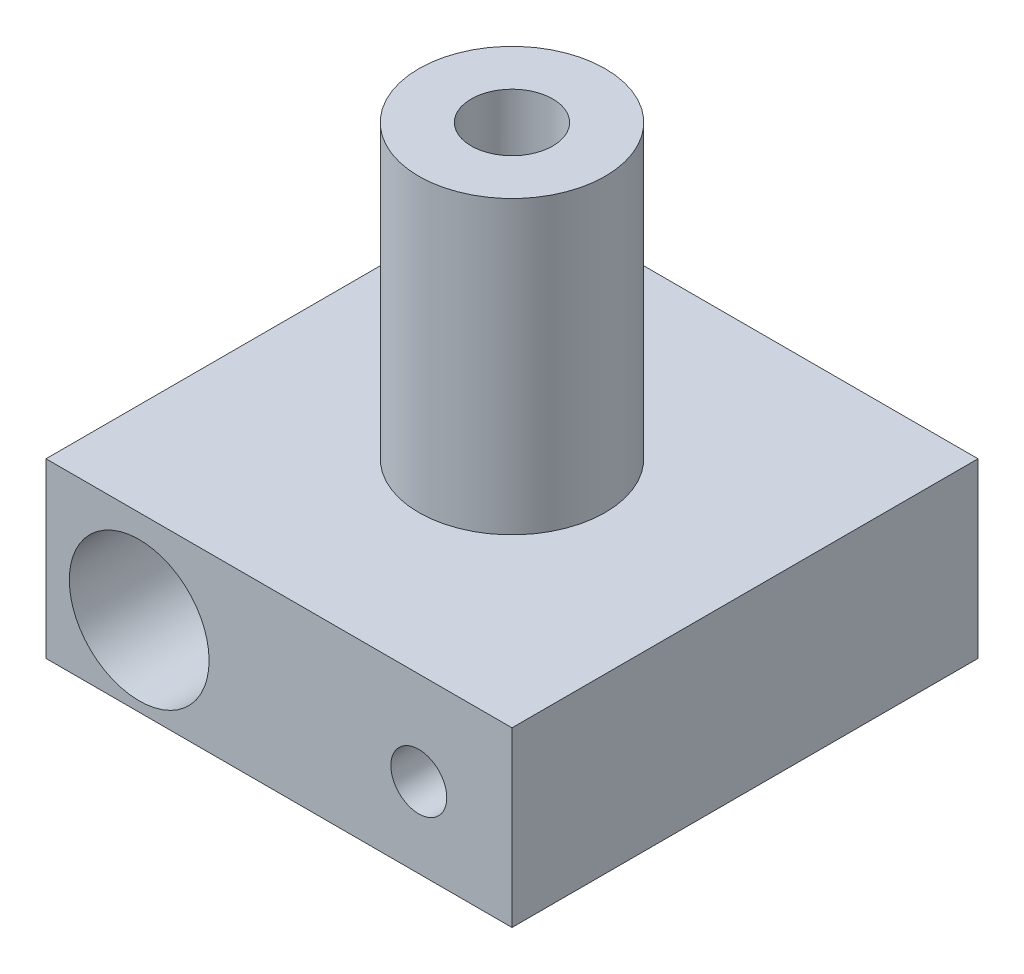
SolidWorks part; units mm, degrees
material "Ottone"
ref_plane "Piano frontale" through (0, 0, 0) normal (0, 0, 1) x (1, 0, 0)
ref_plane "Piano superiore" through (0, 0, 0) normal (0, 1, 0) x (1, 0, 0)
ref_plane "Piano destro" through (0, 0, 0) normal (1, 0, 0) x (0, 0, -1)
sketch "Schizzo1" plane through (0, 0, 0) normal (0, 0, 1) x (1, 0, 0)
  line L0 (-0.15, 0) -> (-0.15, -4)
  line L1 (-0.15, -4) -> (-0.5, -4)
  line L2 (-0.5, -4) -> (-4, -1.5)
  line L3 (-4, -1.5) -> (-4, 0)
  line L4 (-4, 0) -> (-0.15, 0)
  line L5 (0, -26.5282) -> (0, 14.9614) construction
  dimension "D1" = 0.3
  dimension "D2" = 4
  dimension "D3" = 8
  dimension "D4" = 1
  dimension "D5" = 1.5
revolve "Rivoluzione1" add sketch "Schizzo1" angle 360 about L5
sketch "Schizzo2" plane through (0, 0, 0) normal (0, 1, 0) x (1, 0, 0)
  line L0 (0, 0) -> (0, -10.5487) construction
  line L6 (10, -10) -> (-10, -10)
  line L7 (10, -10) -> (10, 10)
  line L8 (10, 10) -> (-10, 10)
  line L9 (-10, -10) -> (-10, 10)
  line L10 (10, -10) -> (-10, 10) construction
  line L11 (10, 10) -> (-10, -10) construction
  circle A1 centre (0, 0) radius 0.15 construction
  circle A2 centre (0, 0) radius 0.15
  dimension "D1" = 20
  dimension "D2" = 20
extrude "Estrusione-Estrusione1" add sketch "Schizzo2" along normal blind 8
sketch "Schizzo3" plane through (0, 8, 0) normal (0, 1, 0) x (1, 0, 0)
  circle A0 centre (0, 0) radius 4
extrude "Estrusione-Sottile1" add sketch "Schizzo3" along normal blind 12.5 thin thin type one direction reverse wall 2.25
sketch "Schizzo4" plane through (0, 0, 10) normal (0, 0, 1) x (1, 0, 0)
  line L0 (-10, 4) -> (10, 4) construction
  line L1 (-10, 8) -> (-10, 0) construction
  line L2 (10, 8) -> (10, 0) construction
  circle A0 centre (-6, 4) radius 3
  circle A1 centre (6, 4) radius 1.2
  dimension "D1" = 4
  dimension "D2" = 6
  dimension "D3" = 2.4
  dimension "D4" = 4
extrude "Taglio-Estrusione1" cut sketch "Schizzo4" against normal up to next
sketch "Schizzo5" plane through (0, 0, -10) normal (0, 0, -1) x (-1, 0, 0)
  circle A0 centre (-6, 4) radius 3
hole_wizard "Foro filettato M6x1.0-1" positions "Schizzo7" profile "Schizzo6" tap size "M6x1.0" standard "Ansi Metric"
sketch "Schizzo7" plane through (0, 0, -10) normal (0, 0, -1) x (-1, 0, 0)
  point P1 (-6, 4)
sketch "Schizzo6" plane through (6, 4, -10) normal (1, 0, 0) x (0, 1, 0)
  line L0 (0, 0) -> (0, 13.5022)
  line L1 (0, 13.5022) -> (2.5, 12)
  line L2 (2.5, 12) -> (2.5, 0.525)
  line L3 (2.5, 0.525) -> (3.025, 0)
  line L5 (3.025, 0) -> (0, 0)
  line L6 (-2.5, 0.525) -> (-3.025, 0) construction
  line L10 (0, 13.5022) -> (-2.5, 12) construction
  line L11 (0, -6.35) -> (0, 107.95) construction
  dimension "Tap Drill Dia." = 5
  dimension "Tap Drill Depth" = 12
  dimension "Near C'Sink Dia." = 6.05
  dimension "Near C'Sink Angle" = 90
  dimension "Drill Angle" = 118
cosmetic thread "Filettatura del foro1" parameters "D1"=12, "D2"=6
chamfer "Smusso1" distance 1 angle 30 4 edges at (0, 0, 10) (10, 0, 0) (0, 0, -10) (-10, 0, 0) first distance on face at (0, 0, 0)
equation "\"50di\"=45"
